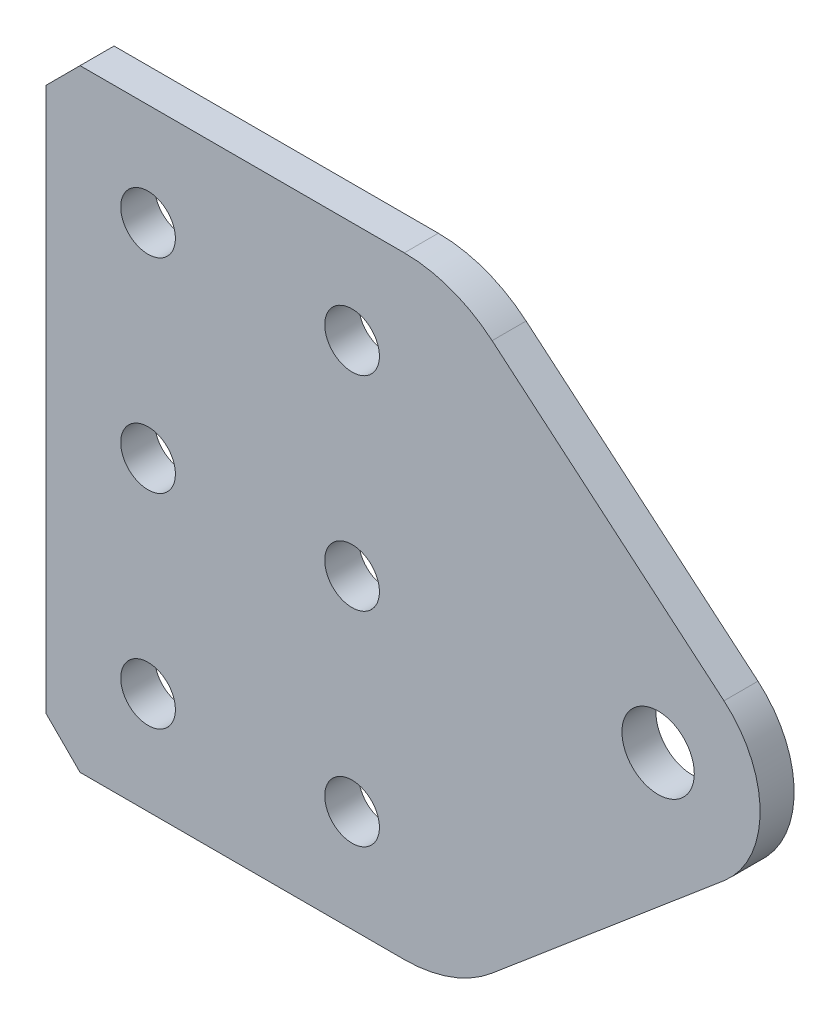
SolidWorks part; units mm, degrees
material "6061-T6 (SS)"
ref_plane "Front Plane" through (0, 0, 0) normal (0, 0, 1) x (1, 0, 0)
ref_plane "Top Plane" through (0, 0, 0) normal (0, 1, 0) x (1, 0, 0)
ref_plane "Right Plane" through (0, 0, 0) normal (1, 0, 0) x (0, 0, -1)
sketch "Sketch1" plane through (0, 0, 0) normal (0, 0, 1) x (1, 0, 0)
  line L0 (0, 0) -> (33.4515, 0)
  line L1 (41.6501, 3.0009) -> (63.299, 21.3007)
  line L2 (63.299, 35.8493) -> (41.6501, 54.1491)
  line L3 (33.4515, 57.15) -> (0, 57.15)
  line L4 (0, 57.15) -> (0, 0)
  arc A0 (63.299, 21.3007) -> (63.299, 35.8493) centre (57.15, 28.575) ccw
  circle A1 centre (57.15, 28.575) radius 3.3782
  arc A2 (33.4515, 0) -> (41.6501, 3.0009) centre (33.4515, 12.7) ccw
  arc A3 (41.6501, 54.1491) -> (33.4515, 57.15) centre (33.4515, 44.45) ccw
  point P11 (38.1, 0)
  dimension "D3" = 19.05
  dimension "D4" = 9.525
  dimension "D5" = 6.7564
  dimension "D6" = 12.7
  dimension "D1" = 57.15
  dimension "D2" = 38.1
extrude "Boss-Extrude1" add sketch "Sketch1" along normal blind 3.175
hole_wizard "#10 Clearance Hole1" positions "Sketch2" profile "Sketch3" hole size "#10" standard "ANSI Inch" end condition through all
sketch "Sketch2" plane through (0, 0, 3.175) normal (0, 0, 1) x (1, 0, 0)
  line L0 (0, 9.525) -> (9.525, 9.525) construction
  line L1 (0, 57.15) -> (0, 0) construction
  line L3 (28.575, 9.525) -> (38.1, 9.525) construction
  line L9 (38.1, 9.525) -> (38.1, 0) construction
  line L11 (41.6501, 3.0009) -> (63.299, 21.3007) construction
  line L12 (0, 0) -> (33.4515, 0) construction
  circle A0 centre (57.15, 28.575) radius 3.3782 construction
  circle A1 centre (57.15, 28.575) radius 3.3782
  point P0 (28.575, 28.575)
  point P2 (9.525, 28.575)
  point P4 (9.525, 47.625)
  point P6 (28.575, 47.625)
  point P8 (28.575, 9.525)
  point P10 (9.525, 9.525)
  dimension "D1" = 19.05
  dimension "D2" = 19.05
  dimension "D3" = 19.05
sketch "Sketch3" plane through (28.575, 28.575, 3.175) normal (1, 0, 0) x (0, -1, 0)
  line L0 (0, 0) -> (0, 3.175)
  line L1 (0, 3.175) -> (2.5527, 3.175)
  line L2 (2.5527, 3.175) -> (2.5527, 0)
  line L5 (2.5527, 0) -> (0, 0)
  line L11 (0, -6.35) -> (0, 107.95) construction
  dimension "Thru Hole Dia." = 5.1054
  dimension "Thru Hole Depth" = 3.175
chamfer "Chamfer1" distance 3.175 angle 45 2 edges at (0, 0, 1.5875) (0, 57.15, 1.5875)
